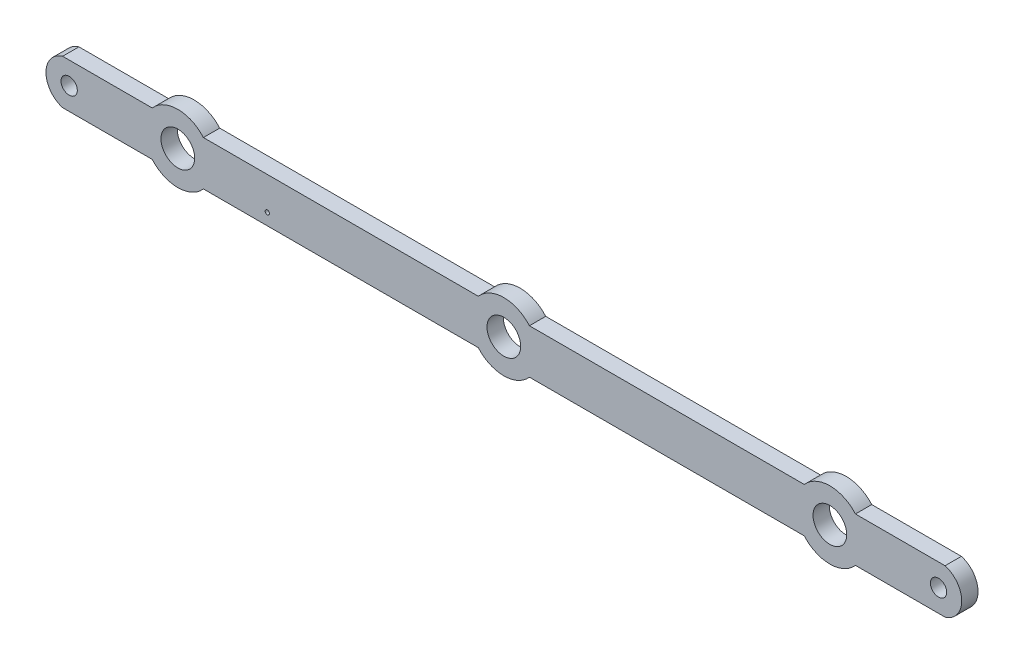
SolidWorks part; units mm, degrees
ref_plane "Front Plane" through (0, 0, 0) normal (0, 0, 1) x (1, 0, 0)
ref_plane "Top Plane" through (0, 0, 0) normal (0, 1, 0) x (1, 0, 0)
ref_plane "Right Plane" through (0, 0, 0) normal (1, 0, 0) x (0, 0, -1)
sketch "Sketch1" plane through (0, 0, 0) normal (0, 0, 1) x (1, 0, 0)
  line L0 (-80, 0) -> (-60, 0) construction
  line L5 (-31.34, 0) -> (-31.34, 4.2698) construction
  line L6 (-60, 0) -> (0, 0) construction
  line L7 (-81.2017, 4.0974) -> (-64.7063, 4.0974)
  line L8 (-81.2017, -4.0974) -> (-64.7063, -4.0974)
  line L9 (-55.2937, 4.0974) -> (-4.7063, 4.0974)
  line L10 (-55.2937, -4.0974) -> (-4.7063, -4.0974)
  line L11 (4.7063, 4.0974) -> (55.2937, 4.0974)
  line L12 (4.7063, -4.0974) -> (55.2937, -4.0974)
  line L13 (60, 0) -> (0, 0) construction
  line L14 (64.7063, 4.0974) -> (81.2017, 4.0974)
  line L15 (64.7063, -4.0974) -> (81.2017, -4.0974)
  line L16 (60, 0) -> (80, 0) construction
  circle A0 centre (-60, 0) radius 3.1
  circle A1 centre (0, 0) radius 3.1
  circle A2 centre (60, 0) radius 3.1
  circle A3 centre (80, 0) radius 1.5
  circle A4 centre (-80, 0) radius 1.5
  circle A5 centre (-43.5336, -1.9489) radius 0.3903
  arc A6 (-81.2017, 4.0974) -> (-81.2017, -4.0974) centre (-80, 0) ccw
  arc A7 (-64.7063, 4.0974) -> (-55.2937, 4.0974) centre (-60, 0) cw
  arc A8 (-64.7063, -4.0974) -> (-55.2937, -4.0974) centre (-60, 0) ccw
  arc A9 (4.7063, 4.0974) -> (-4.7063, 4.0974) centre (0, 0) ccw
  arc A10 (-4.7063, -4.0974) -> (4.7063, -4.0974) centre (0, 0) ccw
  arc A11 (64.7063, 4.0974) -> (55.2937, 4.0974) centre (60, 0) ccw
  arc A12 (55.2937, -4.0974) -> (64.7063, -4.0974) centre (60, 0) ccw
  arc A13 (81.2017, 4.0974) -> (81.2017, -4.0974) centre (80, 0) cw
  point P0 (0, 0)
  dimension "D1" = 6.2
  dimension "D2" = 3
  dimension "D8" = 4.27
  dimension "D10" = 6.24
  dimension "D5" = 160
  dimension "D3" = 20
  dimension "D4" = 28.66
  dimension "D6" = 60
extrude "Boss-Extrude1" add sketch "Sketch1" along normal blind 3
